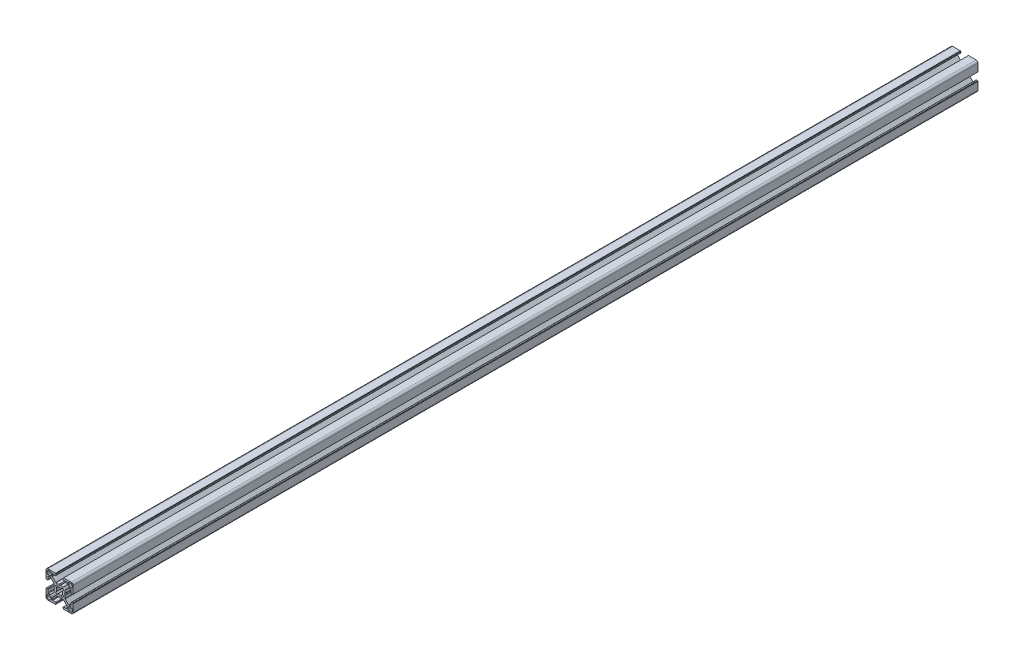
SolidWorks part; units mm, degrees
ref_plane "Front Plane" through (0, 0, 0) normal (0, 0, 1) x (1, 0, 0)
ref_plane "Top Plane" through (0, 0, 0) normal (0, 1, 0) x (1, 0, 0)
ref_plane "Right Plane" through (0, 0, 0) normal (1, 0, 0) x (0, 0, -1)
sketch "Sketch1" plane through (0, 0, 0) normal (0, 0, 1) x (1, 0, 0)
  line L0 (-15, 0) -> (15, 0) construction
  line L1 (0, -15) -> (0, 15) construction
  line L2 (-4.5, 15) -> (4.5, 15) construction
  line L3 (-4, -15) -> (4, -15) construction
  line L4 (-4.5, 15) -> (-4.5, 14.5)
  line L5 (-4.5, 14.5) -> (-4, 14.5)
  line L6 (-4, 14.5) -> (-4, 13.29)
  line L7 (-4.5, 12.79) -> (-7.7675, 12.79)
  line L8 (-8.2675, 12.29) -> (-8.2675, 10.2707)
  line L9 (-8.1211, 9.9171) -> (-4.3504, 6.1464)
  line L10 (-3.9968, 6) -> (0, 6)
  line L11 (0, 0) -> (-15, 15) construction
  line L12 (-4.5, 15) -> (-12.968, 15)
  line L14 (-12.705, 9.5135) -> (-10.5135, 9.5135)
  line L15 (-13.705, 10.5135) -> (-13.705, 12.705)
  line L16 (-12.705, 13.705) -> (-10.5135, 13.705)
  line L17 (-9.5135, 10.5135) -> (-9.5135, 12.705)
  line L18 (-13.705, 9.5135) -> (-9.5135, 13.705) construction
  line L19 (-13.705, 13.705) -> (-9.5135, 9.5135) construction
  line L20 (-3.1568, 4.5038) -> (-1.5303, 3.1477) construction
  line L21 (-4.5038, 3.1568) -> (-3.1477, 1.5303) construction
  line L22 (-6, 3.9968) -> (-6, 0)
  line L23 (-9.9171, 8.1211) -> (-6.1464, 4.3504)
  line L24 (-15, 4.5) -> (-15, 12.968)
  line L25 (-12.29, 8.2675) -> (-10.2707, 8.2675)
  line L26 (-12.79, 4.5) -> (-12.79, 7.7675)
  line L27 (-14.5, 4) -> (-13.29, 4)
  line L28 (-14.5, 4.5) -> (-14.5, 4)
  line L29 (-15, 4.5) -> (-14.5, 4.5)
  circle A0 centre (0, 0) radius 3.5
  arc A1 (-12.968, 15) -> (-15, 12.968) centre (-12.968, 12.968) ccw
  circle A2 centre (0, 0) radius 5.5 construction
  arc A3 (-10.5135, 9.5135) -> (-9.5135, 10.5135) centre (-10.5135, 10.5135) ccw
  arc A4 (-13.705, 12.705) -> (-12.705, 13.705) centre (-12.705, 12.705) cw
  arc A5 (-10.5135, 13.705) -> (-9.5135, 12.705) centre (-10.5135, 12.705) cw
  arc A6 (-12.705, 9.5135) -> (-13.705, 10.5135) centre (-12.705, 10.5135) cw
  arc A7 (-12.79, 4.5) -> (-13.29, 4) centre (-13.29, 4.5) cw
  arc A8 (-12.29, 8.2675) -> (-12.79, 7.7675) centre (-12.29, 7.7675) ccw
  arc A9 (-9.9171, 8.1211) -> (-10.2707, 8.2675) centre (-10.2707, 7.7675) ccw
  arc A10 (-6, 3.9968) -> (-6.1464, 4.3504) centre (-6.5, 3.9968) ccw
  arc A11 (-4.3504, 6.1464) -> (-3.9968, 6) centre (-3.9968, 6.5) ccw
  arc A12 (-4, 13.29) -> (-4.5, 12.79) centre (-4.5, 13.29) cw
  arc A13 (-7.7675, 12.79) -> (-8.2675, 12.29) centre (-7.7675, 12.29) ccw
  arc A14 (-8.2675, 10.2707) -> (-8.1211, 9.9171) centre (-7.7675, 10.2707) ccw
  point P4 (0, 0)
  point P8 (0, 0)
  point P13 (0, 15)
  point P15 (0, -15)
  point P16 (0, 6)
  point P23 (-11.6092, 11.6093)
  point P26 (0, 6)
  point P62 (-12.79, 4)
  point P65 (-12.79, 8.2675)
  point P68 (-10.0636, 8.2675)
  point P71 (-6, 4.2039)
  point P74 (-4.2039, 6)
  point P77 (-4, 12.79)
  point P80 (-8.2675, 12.79)
  point P83 (-8.2675, 10.0636)
  dimension "Center Hole Diameter" = 7
  dimension "D11" = 2.032
  dimension "D9" = 11
  dimension "D13" = 1
  dimension "D14" = 0.5
  dimension "Rail Height" = 30
  dimension "Rail Width" = 30
  dimension "T-Slot Width" = 8
  dimension "T-Slot Depth" = 9
  dimension "D1" = 9
  dimension "D2" = 45
  dimension "D3" = 8
  dimension "D4" = 2.21
  dimension "D5" = 16.535
  dimension "D7" = 2.54
  dimension "D6" = 1.295
  dimension "D8" = 1.246
  dimension "D10" = 10.36
  dimension "D12" = 1.905
sketch "Sketch2" plane through (0, 0, 0) normal (1, 0, 0) x (0, 0, -1)
  line L0 (-76.2, 0) -> (76.2, 0) construction
  line L2 (0, -15) -> (0, 15) construction
  line L3 (0, -15) -> (0, 15) construction
  line L4 (-76.2, -15) -> (-76.2, 15) construction
  line L5 (76.2, -15) -> (76.2, 15) construction
  point P0 (-38.7, 0)
  point P3 (0, 0)
  point P4 (38.7, 0)
  point P12 (-76.2, 0)
  point P14 (76.2, 0)
  dimension "Length" = 152.4
  dimension "D1" = 37.5
sketch "Sketch3" plane through (0, 0, 0) normal (0, 0, 1) x (1, 0, 0)
  line L0 (-4.5038, 3.1568) -> (-3.1477, 1.5303)
  line L1 (0, 3.5) -> (0, 5.5)
  line L2 (-5.5, 0) -> (-3.5, 0)
  line L7 (-6, 3.9968) -> (-6, 0) construction
  line L31 (-9.9171, 8.1211) -> (-6.1464, 4.3504) construction
  line L117 (-12.29, 8.2675) -> (-10.2707, 8.2675) construction
  line L118 (-12.79, 4.5) -> (-12.79, 7.7675) construction
  line L157 (-12.705, 9.5135) -> (-10.5135, 9.5135)
  line L158 (-9.5135, 10.5135) -> (-9.5135, 12.705)
  line L163 (-10.5135, 13.705) -> (-12.705, 13.705)
  line L164 (-13.705, 12.705) -> (-13.705, 10.5135)
  line L165 (-12.705, 9.5135) -> (-10.5135, 9.5135)
  line L166 (-9.5135, 10.5135) -> (-9.5135, 12.705)
  line L167 (-10.5135, 13.705) -> (-12.705, 13.705)
  line L168 (-13.705, 12.705) -> (-13.705, 10.5135)
  line L169 (-14.5, 4) -> (-13.29, 4) construction
  line L170 (-14.5, 4.5) -> (-14.5, 4) construction
  line L171 (-15, 4.5) -> (-14.5, 4.5) construction
  line L172 (-15, 4.5) -> (-15, 12.968) construction
  line L173 (-4.5, 15) -> (-12.968, 15) construction
  line L174 (-4.5, 15) -> (-4.5, 14.5) construction
  line L175 (-4.5, 14.5) -> (-4, 14.5) construction
  line L176 (-4, 14.5) -> (-4, 13.29) construction
  line L177 (-4.5, 12.79) -> (-7.7675, 12.79) construction
  line L178 (-8.2675, 12.29) -> (-8.2675, 10.2707) construction
  line L179 (-8.1211, 9.9171) -> (-4.3504, 6.1464) construction
  line L180 (-3.9968, 6) -> (0, 6) construction
  line L181 (-6, 3.9968) -> (-6, 0.866)
  line L182 (-9.9171, 8.1211) -> (-6.1464, 4.3504)
  line L183 (-12.29, 8.2675) -> (-10.2707, 8.2675)
  line L184 (-12.79, 4.5) -> (-12.79, 7.7675)
  line L185 (-14.5, 4) -> (-13.29, 4)
  line L186 (-14.5, 4.5) -> (-14.5, 4)
  line L187 (-15, 4.5) -> (-14.5, 4.5)
  line L188 (-15, 4.5) -> (-15, 12.968)
  line L189 (-4.5, 15) -> (-12.968, 15)
  line L190 (-4.5, 15) -> (-4.5, 14.5)
  line L191 (-4.5, 14.5) -> (-4, 14.5)
  line L192 (-4, 14.5) -> (-4, 13.29)
  line L193 (-4.5, 12.79) -> (-7.7675, 12.79)
  line L194 (-8.2675, 12.29) -> (-8.2675, 10.2707)
  line L195 (-8.1211, 9.9171) -> (-4.3504, 6.1464)
  line L196 (-3.9968, 6) -> (-0.866, 6)
  line L197 (-0.866, 6) -> (0, 5.5)
  line L198 (0, -15) -> (0, 15) construction
  line L199 (0, 0) -> (-15, 15) construction
  line L200 (0, 0) -> (-15, 15) construction
  line L201 (-3.1568, 4.5038) -> (-1.5303, 3.1477) construction
  line L202 (-3.1568, 4.5038) -> (-1.5303, 3.1477)
  line L203 (-6, 0.866) -> (-5.5, 0)
  line L204 (-15, 0) -> (15, 0) construction
  line L205 (-15, 0) -> (15, 0) construction
  line L206 (0, -15) -> (0, 15) construction
  arc A0 (-3.5, 0) -> (-3.1477, 1.5303) centre (0, 0) cw
  arc A10 (-6, 3.9968) -> (-6.1464, 4.3504) centre (-6.5, 3.9968) ccw construction
  circle A16 centre (0, 0) radius 3.5
  arc A18 (0, 3.5) -> (-1.5303, 3.1477) centre (0, 0) ccw
  arc A20 (-9.9171, 8.1211) -> (-10.2707, 8.2675) centre (-10.2707, 7.7675) ccw construction
  arc A22 (-12.29, 8.2675) -> (-12.79, 7.7675) centre (-12.29, 7.7675) ccw construction
  arc A28 (-13.29, 4) -> (-12.79, 4.5) centre (-13.29, 4.5) ccw construction
  arc A29 (-10.5135, 9.5135) -> (-9.5135, 10.5135) centre (-10.5135, 10.5135) ccw
  arc A30 (-9.5135, 12.705) -> (-10.5135, 13.705) centre (-10.5135, 12.705) ccw
  arc A31 (-12.705, 13.705) -> (-13.705, 12.705) centre (-12.705, 12.705) ccw
  arc A32 (-13.705, 10.5135) -> (-12.705, 9.5135) centre (-12.705, 10.5135) ccw
  arc A33 (-10.5135, 9.5135) -> (-9.5135, 10.5135) centre (-10.5135, 10.5135) ccw
  arc A34 (-9.5135, 12.705) -> (-10.5135, 13.705) centre (-10.5135, 12.705) ccw
  arc A35 (-12.705, 13.705) -> (-13.705, 12.705) centre (-12.705, 12.705) ccw
  arc A36 (-13.705, 10.5135) -> (-12.705, 9.5135) centre (-12.705, 10.5135) ccw
  arc A37 (-12.968, 15) -> (-15, 12.968) centre (-12.968, 12.968) ccw construction
  arc A38 (-4.5, 12.79) -> (-4, 13.29) centre (-4.5, 13.29) ccw construction
  arc A39 (-7.7675, 12.79) -> (-8.2675, 12.29) centre (-7.7675, 12.29) ccw construction
  arc A40 (-8.2675, 10.2707) -> (-8.1211, 9.9171) centre (-7.7675, 10.2707) ccw construction
  arc A41 (-4.3504, 6.1464) -> (-3.9968, 6) centre (-3.9968, 6.5) ccw construction
  arc A42 (-6, 3.9968) -> (-6.1464, 4.3504) centre (-6.5, 3.9968) ccw
  arc A43 (-9.9171, 8.1211) -> (-10.2707, 8.2675) centre (-10.2707, 7.7675) ccw
  arc A44 (-12.29, 8.2675) -> (-12.79, 7.7675) centre (-12.29, 7.7675) ccw
  arc A45 (-13.29, 4) -> (-12.79, 4.5) centre (-13.29, 4.5) ccw
  arc A46 (-12.968, 15) -> (-15, 12.968) centre (-12.968, 12.968) ccw
  arc A47 (-4.5, 12.79) -> (-4, 13.29) centre (-4.5, 13.29) ccw
  arc A48 (-7.7675, 12.79) -> (-8.2675, 12.29) centre (-7.7675, 12.29) ccw
  arc A49 (-8.2675, 10.2707) -> (-8.1211, 9.9171) centre (-7.7675, 10.2707) ccw
  arc A50 (-4.3504, 6.1464) -> (-3.9968, 6) centre (-3.9968, 6.5) ccw
  circle A51 centre (0, 0) radius 5.5 construction
  arc A52 (-3.1568, 4.5038) -> (-4.5038, 3.1568) centre (0, 0) ccw
  dimension "D3" = 60
  dimension "D4" = 60
  dimension "D1" = 0
  dimension "D2" = 0
extrude "Boss-Extrude1" add sketch "Sketch3" along normal mid plane 1000
pattern_circular "CirPattern1" count 4 over 360 about axis through (0, 0, 76.2) along (0, 0, -1) of "Boss-Extrude1"
ref_plane "Contact Plane1" through (15, 0, 0) normal (1, 0, 0) x (0, 0, -1)
ref_plane "Contact Plane2" through (0, -15, 0) normal (0, 1, 0) x (1, 0, 0)
ref_plane "Contact Plane3" through (-15, 0, 0) normal (1, 0, 0) x (0, 0, -1)
ref_plane "Contact Plane4" through (0, 15, 0) normal (0, 1, 0) x (1, 0, 0)
equation "\"D1@Sketch2\" = \"Rail Height@Sketch1\" * 1.25"
equation "\"D1@Sketch1\"=\"T-Slot Width@Sketch1\"+1mm"
equation "\"D3@Sketch1\"=\"T-Slot Width@Sketch1\""
equation "\"D1@Boss-Extrude1\"=\"Length\""
equation "\"Length\" = 1000mm"
